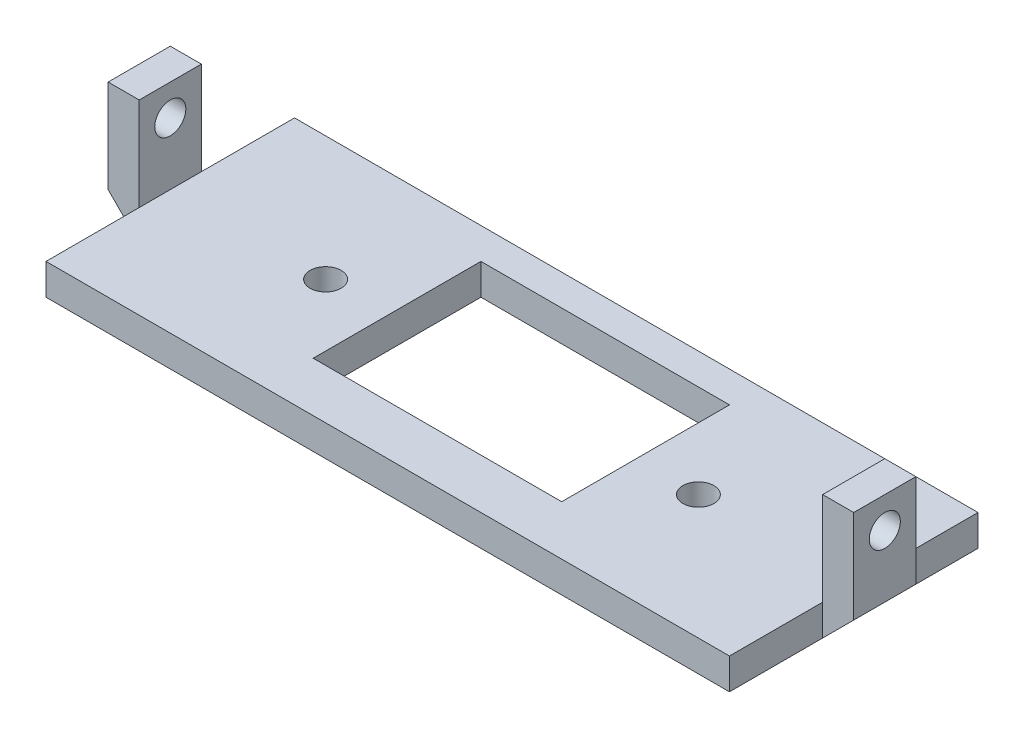
SolidWorks part; units mm, degrees
ref_plane "Front Plane" through (0, 0, 0) normal (0, 0, 1) x (1, 0, 0)
ref_plane "Top Plane" through (0, 0, 0) normal (0, 1, 0) x (1, 0, 0)
ref_plane "Right Plane" through (0, 0, 0) normal (1, 0, 0) x (0, 0, -1)
sketch "Sketch1" plane through (0, 0, 0) normal (0, 1, 0) x (1, 0, 0)
  line L1 (-60, 42.5) -> (60, 42.5)
  line L2 (-60, 42.5) -> (-60, -42.5)
  line L3 (-60, -42.5) -> (60, -42.5)
  line L4 (60, 42.5) -> (60, -42.5)
  line L5 (-60, 42.5) -> (60, -42.5) construction
  line L6 (-60, -42.5) -> (60, 42.5) construction
  point P0 (0, 0)
  dimension "D1" = 120
  dimension "D2" = 85
extrude "Boss-Extrude1" add sketch "Sketch1" along normal blind 5
sketch "Sketch2" plane through (0, 5, 0) normal (0, 1, 0) x (1, 0, 0)
  line L0 (-60, 42.5) -> (-60, -42.5) construction
  line L1 (-60, 17.5) -> (-55, 17.5)
  line L2 (-60, 17.5) -> (-60, 7.5)
  line L3 (-60, 7.5) -> (-55, 7.5)
  line L4 (-55, 17.5) -> (-55, 7.5)
  line L6 (-60, -7.5) -> (-55, -7.5)
  line L7 (-60, -7.5) -> (-60, -17.5)
  line L8 (-60, -17.5) -> (-55, -17.5)
  line L9 (-55, -7.5) -> (-55, -17.5)
  line L10 (-60, 12.5) -> (-55, 12.5) construction
  line L11 (-60, -12.5) -> (-55, -12.5) construction
  line L14 (60, 42.5) -> (-60, 42.5) construction
  line L16 (0, 0) -> (0, -27.3364) construction
  line L17 (60, -12.5) -> (55, -12.5) construction
  line L18 (60, 12.5) -> (55, 12.5) construction
  line L19 (55, -7.5) -> (55, -17.5)
  line L20 (60, -17.5) -> (55, -17.5)
  line L21 (60, -7.5) -> (60, -17.5)
  line L22 (60, -7.5) -> (55, -7.5)
  line L23 (55, 17.5) -> (55, 7.5)
  line L24 (60, 7.5) -> (55, 7.5)
  line L25 (60, 17.5) -> (60, 7.5)
  line L26 (60, 17.5) -> (55, 17.5)
  dimension "D1" = 30
  dimension "D2" = 10
  dimension "D3" = 10
  dimension "D4" = 25
  dimension "D5" = 5
  dimension "D6" = 5
extrude "Boss-Extrude2" add sketch "Sketch2" along normal blind 15
sketch "Sketch3" plane through (-60, 0, 0) normal (-1, 0, 0) x (0, 0, 1)
  line L0 (7.5, 20) -> (17.5, 20) construction
  line L1 (-17.5, 20) -> (-7.5, 20) construction
  line L2 (-17.5, 20) -> (-17.5, 5) construction
  line L3 (7.5, 20) -> (7.5, 5) construction
  circle A0 centre (-12.5, 15) radius 2.5
  circle A1 centre (12.5, 15) radius 2.5
  dimension "D1" = 5
  dimension "D2" = 5
  dimension "D3" = 5
  dimension "D4" = 5
  dimension "D5" = 5
  dimension "D6" = 5
extrude "Cut-Extrude1" cut sketch "Sketch3" against normal through all
sketch "Sketch5" plane through (0, 5, 0) normal (0, 1, 0) x (1, 0, 0)
  line L0 (0, 0) -> (0, -37.502) construction
  line L1 (-60, 42.5) -> (-55, 42.5)
  line L2 (-60, 42.5) -> (-60, 17.5)
  line L3 (-60, 17.5) -> (-55, 17.5)
  line L4 (-55, 42.5) -> (-55, 17.5)
  line L5 (-60, 7.5) -> (-55, 7.5)
  line L6 (-60, 7.5) -> (-60, -7.5)
  line L7 (-60, -7.5) -> (-55, -7.5)
  line L8 (-55, 7.5) -> (-55, -7.5)
  line L9 (-55, -17.5) -> (-60, -17.5)
  line L10 (-55, -17.5) -> (-55, -42.5)
  line L11 (-55, -42.5) -> (-60, -42.5)
  line L12 (-60, -17.5) -> (-60, -42.5)
  line L13 (60, -17.5) -> (60, -42.5)
  line L14 (55, -42.5) -> (60, -42.5)
  line L15 (55, -17.5) -> (55, -42.5)
  line L16 (55, -17.5) -> (60, -17.5)
  line L17 (55, 7.5) -> (55, -7.5)
  line L18 (60, -7.5) -> (55, -7.5)
  line L19 (60, 7.5) -> (60, -7.5)
  line L20 (60, 7.5) -> (55, 7.5)
  line L21 (55, 42.5) -> (55, 17.5)
  line L22 (60, 17.5) -> (55, 17.5)
  line L23 (60, 42.5) -> (60, 17.5)
  line L24 (60, 42.5) -> (55, 42.5)
extrude "Cut-Extrude2" cut sketch "Sketch5" against normal through all
chamfer "Chamfer1" distance 5 angle 45 4 edges at (-60, 0, 12.5) (-60, 0, -12.5) (60, 0, -12.5) (60, 0, 12.5)
sketch "Sketch6" plane through (0, 0, 0) normal (0, -1, 0) x (1, 0, 0)
  line L0 (-55, 42.5) -> (-55, 17.5) construction
  line L1 (-55, -42.5) -> (55, -42.5)
  line L2 (-55, -42.5) -> (-55, -7.5)
  line L3 (-55, -7.5) -> (55, -7.5)
  line L4 (55, -42.5) -> (55, -7.5)
  line L5 (55, 42.5) -> (-55, 42.5)
  line L6 (55, 42.5) -> (55, 32.5)
  line L7 (55, 32.5) -> (-55, 32.5)
  line L8 (-55, 42.5) -> (-55, 32.5)
  line L10 (-60, 17.5) -> (-55, 17.5) construction
  line L12 (-60, -7.5) -> (-55, -7.5)
  line L13 (-60, -7.5) -> (-60, -42.5)
  line L14 (-60, -42.5) -> (-55, -42.5)
  line L15 (-55, -7.5) -> (-55, -42.5)
  line L16 (55, -42.5) -> (60, -42.5)
  line L17 (55, -42.5) -> (55, -7.5)
  line L18 (55, -7.5) -> (60, -7.5)
  line L19 (60, -42.5) -> (60, -7.5)
  line M2 (-55, 42.5) -> (-55, 17.5)
  line M5 (-55, -7.5) -> (-55, -17.5)
  line M6 (-55, -17.5) -> (-55, -42.5)
  line M7 (-55, -42.5) -> (55, -42.5)
  line M8 (55, -42.5) -> (55, -17.5)
  line M9 (55, -17.5) -> (55, -7.5)
  line M12 (55, 17.5) -> (55, 42.5)
  line M13 (55, 42.5) -> (-55, 42.5)
  dimension "D1" = 15
extrude "Cut-Extrude3" cut sketch "Sketch6" against normal through all contours L3 M5 M6 M7 M8 M9 | L13 L14 L12 M6 M5 | L7 M12 M13 M2 | L16 L19 L18 M9 M8 region at (0, 0, -25) region at (-57.5, 0, -25) region at (57.5, 0, -25) region at (0, 0, 37.5)
sketch "Sketch7" plane through (0, 0, 0) normal (0, -1, 0) x (1, 0, 0)
  line L0 (-55, 17.5) -> (-55, 7.5) construction
  line L1 (55, 7.5) -> (55, 17.5) construction
  line L2 (55, 32.5) -> (-55, 32.5) construction
  circle A0 centre (-30, 12.5) radius 2.5
  circle A1 centre (30, 12.5) radius 2.5
  dimension "D1" = 5
  dimension "D2" = 5
  dimension "D3" = 25
  dimension "D4" = 25
  dimension "D5" = 20
  dimension "D6" = 20
extrude "Cut-Extrude4" cut sketch "Sketch7" against normal blind 10
sketch "Sketch8" plane through (0, 0, 0) normal (0, -1, 0) x (-1, 0, 0)
  line L0 (55, 7.5) -> (-55, 7.5) construction
  line L1 (20, -24.5) -> (-20, -24.5)
  line L2 (20, -24.5) -> (20, 2.5)
  line L3 (20, 2.5) -> (-20, 2.5)
  line L4 (-20, -24.5) -> (-20, 2.5)
  line L5 (-55, -32.5) -> (55, -32.5) construction
  line L6 (-55, -7.5) -> (-55, -17.5) construction
  line L7 (55, -32.5) -> (55, -17.5) construction
  dimension "D1" = 5
  dimension "D2" = 8
  dimension "D3" = 35
  dimension "D4" = 35
extrude "Cut-Extrude5" cut sketch "Sketch8" against normal blind 10
